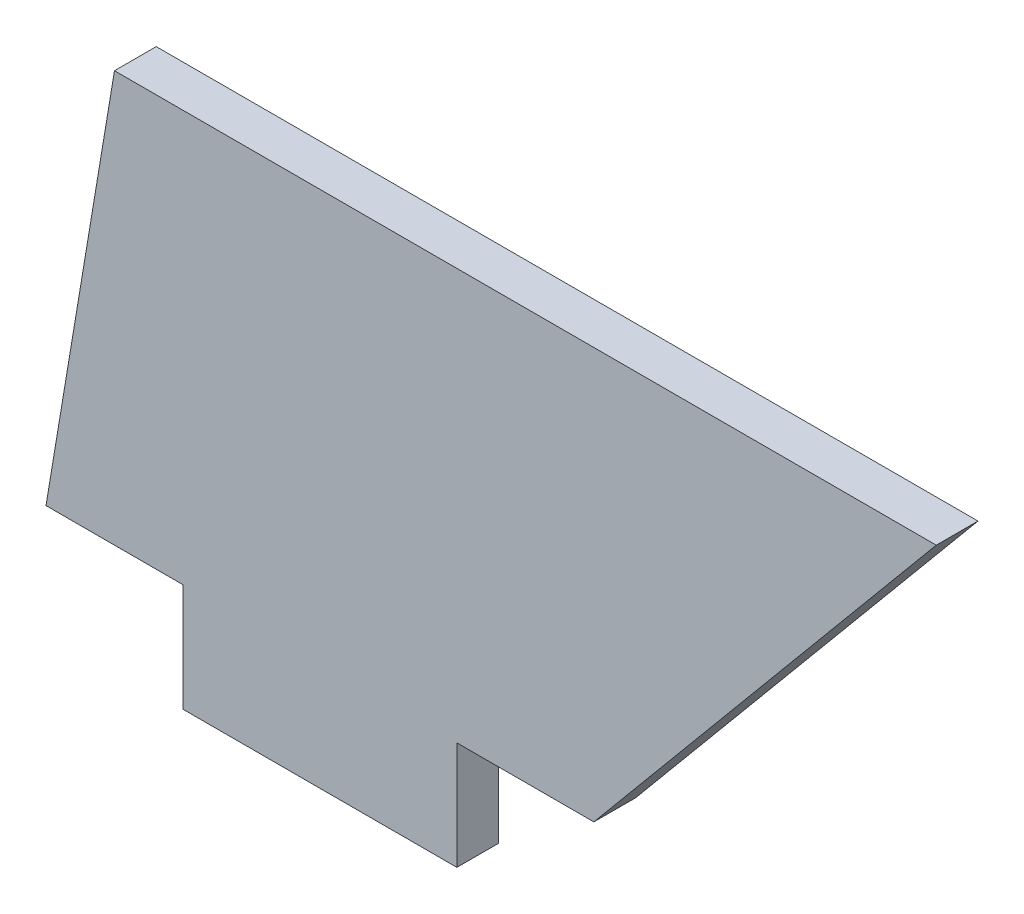
SolidWorks part; units mm, degrees
ref_plane "Front Plane" through (0, 0, 0) normal (0, 0, 1) x (1, 0, 0)
ref_plane "Top Plane" through (0, 0, 0) normal (0, 1, 0) x (1, 0, 0)
ref_plane "Right Plane" through (0, 0, 0) normal (1, 0, 0) x (0, 0, -1)
sketch "Sketch1" plane through (0, 0, 0) normal (0, 0, 1) x (1, 0, 0)
  line L0 (0, 0) -> (10, 0)
  line L1 (10, 0) -> (10, -7.875)
  line L2 (10, -7.875) -> (30, -7.875)
  line L3 (30, -7.875) -> (30, 0)
  line L4 (30, 0) -> (40, 0)
  line L5 (40, 0) -> (65, 30)
  line L6 (65, 30) -> (5, 30)
  line L7 (5, 30) -> (0, 0)
  point P2 (12.2652, 9.2378)
  point P3 (15.9427, -7.875)
  dimension "D1" = 40
  dimension "D2" = 7.875
  dimension "D3" = 20
  dimension "D4" = 30
  dimension "D5" = 60
  dimension "D6" = 5
  dimension "D7" = 10
extrude "Boss-Extrude1" add sketch "Sketch1" along normal blind 3.048
